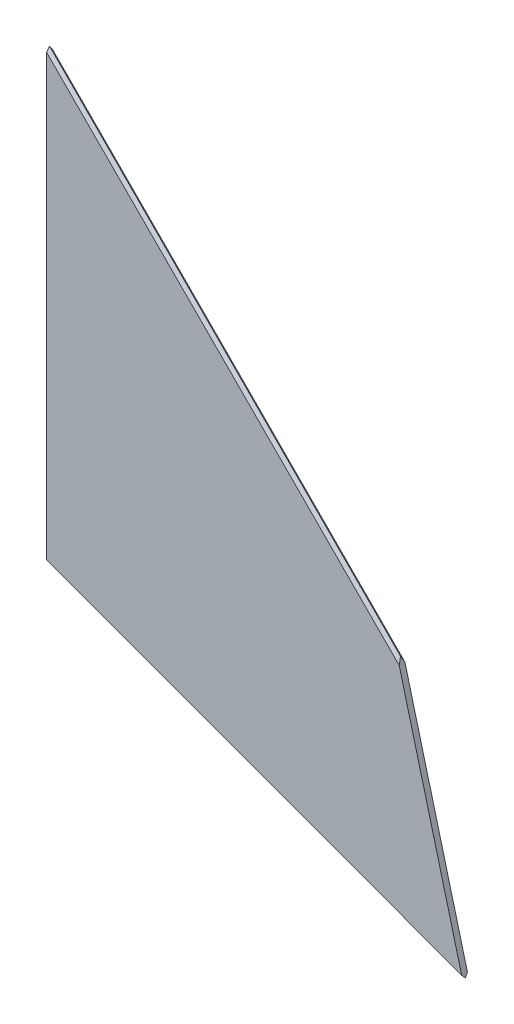
SolidWorks part; units mm, degrees
material "Carbon Fiber"
ref_plane "Front Plane" through (0, 0, 0) normal (0, 0, 1) x (1, 0, 0)
ref_plane "Top Plane" through (0, 0, 0) normal (0, 1, 0) x (1, 0, 0)
ref_plane "Right Plane" through (0, 0, 0) normal (1, 0, 0) x (0, 0, -1)
sketch "Sketch1" plane through (0, 0, 0) normal (0, 0, 1) x (1, 0, 0)
  line L0 (0, 0) -> (0, 234)
  line L1 (0, 234) -> (184, 49)
  line L2 (184, 49) -> (218, -80)
  line L3 (0, 0) -> (218, -80)
  dimension "D1" = 234
  dimension "D2" = 184
  dimension "D3" = 185
  dimension "D4" = 314
  dimension "D5" = 218
extrude "Boss-Extrude1" add sketch "Sketch1" along normal mid plane 3
chamfer "Chamfer1" distance 1.5 angle 45 4 edges at (92, 141.5, -1.5) (92, 141.5, 1.5) (109, -40, -1.5) (109, -40, 1.5)
sketch "Sketch3" plane through (0, 0, 0) normal (0, 1, 0) x (1, 0, 0)
  line L0 (0, 0) -> (-1, 0) construction
  line L2 (0, 0) -> (0, 20)
  line L3 (0, 20) -> (-4.4315, 20)
  line L6 (0, 0) -> (0, -20)
  line L7 (0, -20) -> (-4.4315, -20)
  arc A0 (-4.4315, -20) -> (-4.4315, 20) centre (-61, 0) ccw
  dimension "D1" = 120
  dimension "D2" = 40
  dimension "D3" = 1
extrude "Boss-Extrude2" [suppressed] add sketch "Sketch3" along normal up to vertex (235.6266 mm away) contours L3 A0 L7 L6 L2 up to point (0, 234, 0)
fillet "Fillet1" [suppressed] radius 37
fillet "Fillet3" [suppressed] radius 18
